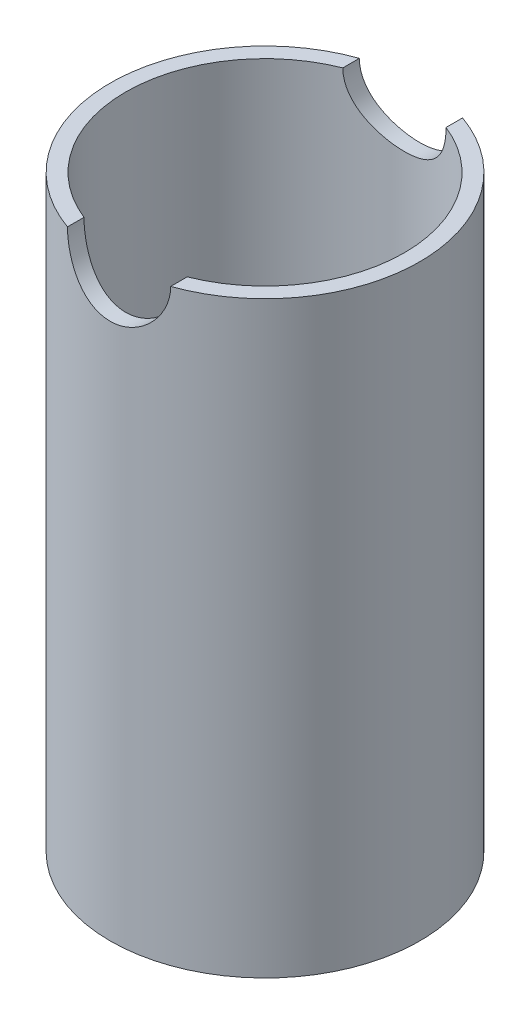
SolidWorks part; units mm, degrees
ref_plane "Front Plane" through (0, 0, 0) normal (0, 0, 1) x (1, 0, 0)
ref_plane "Top Plane" through (0, 0, 0) normal (0, 1, 0) x (1, 0, 0)
ref_plane "Right Plane" through (0, 0, 0) normal (1, 0, 0) x (0, 0, -1)
sketch "Sketch1" plane through (0, 0, 0) normal (0, 1, 0) x (1, 0, 0)
  circle A0 centre (0, 0) radius 3.6
  circle A1 centre (0, 0) radius 15
  circle A2 centre (0, 0) radius 13.5
  dimension "D1" = 7.2
  dimension "D2" = 30
  dimension "D3" = 27
extrude "Boss-Extrude1" add sketch "Sketch1" along normal blind 2 contours A1 A2 | A2 A0 region at (-14.5757, 0, 0) region at (-13.1182, 0, 0)
extrude "Boss-Extrude2" add sketch "Sketch1<3>" along normal blind 57 contours A1 A2 region at (-14.5757, 0, 0)
sketch "Sketch1<3>" plane through (0, 0, 0) normal (0, 1, 0) x (1, 0, 0) same geometry as "Sketch1"
ref_plane "Plane1" through (0, 0, 15) normal (0, 0, 1) x (1, 0, 0)
sketch "Sketch3" plane through (0, 0, 15) normal (0, 0, 1) x (1, 0, 0)
  line L0 (15, 57) -> (-15, 57) construction
  circle A0 centre (0, 57) radius 5
  point P4 (0, 57)
  dimension "D1" = 10
extrude "Cut-Extrude2" cut sketch "Sketch3" against normal blind 57
